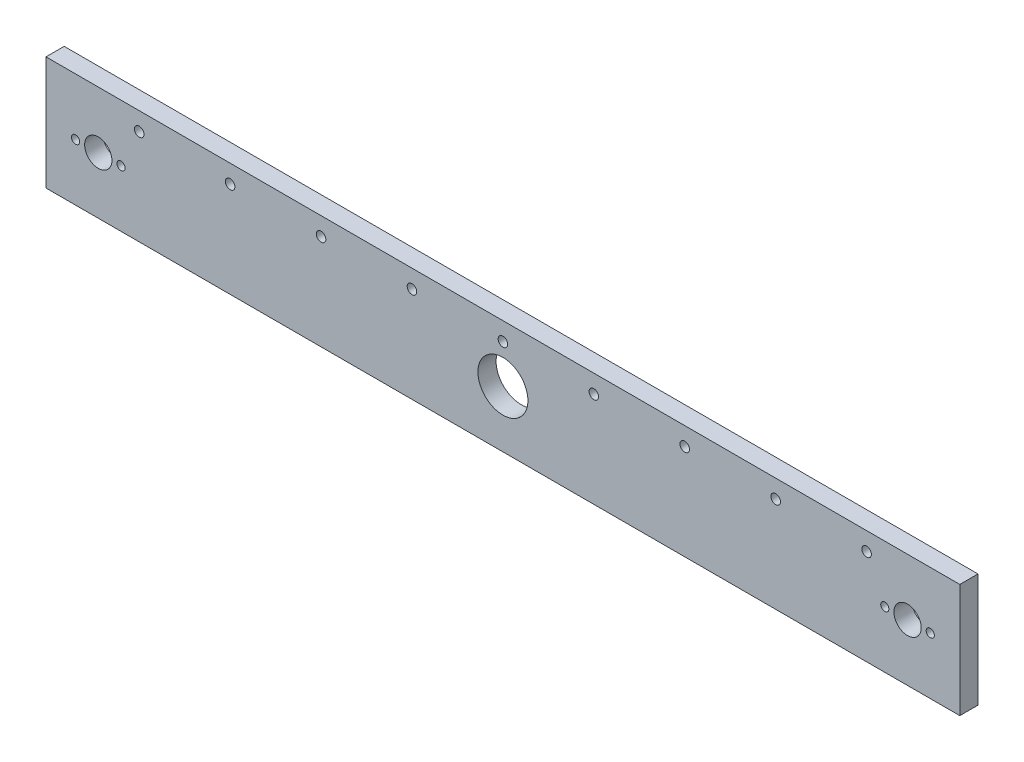
SolidWorks part; units mm, degrees
ref_plane "Front Plane" through (0, 0, 0) normal (0, 0, 1) x (1, 0, 0)
ref_plane "Top Plane" through (0, 0, 0) normal (0, 1, 0) x (1, 0, 0)
ref_plane "Right Plane" through (0, 0, 0) normal (1, 0, 0) x (0, 0, -1)
sketch "Sketch1" plane through (0, 0, 0) normal (0, 0, 1) x (1, 0, 0)
  line L0 (0, 0) -> (-200, 0) construction
  line L1 (-201, -25) -> (201, -25)
  line L2 (-201, -25) -> (-201, 25)
  line L3 (-201, 25) -> (201, 25)
  line L4 (201, -25) -> (201, 25)
  line L5 (-201, -25) -> (201, 25) construction
  line L6 (-201, 25) -> (201, -25) construction
  line L7 (0, 25) -> (0, -26) construction
  circle A0 centre (-178, 0) radius 6
  circle A1 centre (168, 0) radius 1.8
  circle A2 centre (0, 0) radius 11
  circle A3 centre (-188, 0) radius 1.8
  circle A4 centre (-168, 0) radius 1.8
  circle A5 centre (188, 0) radius 1.8
  circle A6 centre (178, 0) radius 6
  circle A7 centre (0, 17) radius 2.1
  circle A8 centre (-40, 17) radius 2.1
  circle A9 centre (-80, 17) radius 2.1
  circle A10 centre (-120, 17) radius 2.1
  circle A11 centre (-160, 17) radius 2.1
  circle A12 centre (40, 17) radius 2.1
  circle A13 centre (80, 17) radius 2.1
  circle A14 centre (120, 17) radius 2.1
  circle A15 centre (160, 17) radius 2.1
  point P0 (0, 0)
  dimension "D1" = 50
  dimension "D2" = 402
  dimension "D3" = 178
  dimension "D4" = 10
  dimension "D5" = 10
  dimension "D6" = 8
  dimension "D7" = 178
extrude "Boss-Extrude1" add sketch "Sketch1" along normal blind 8
